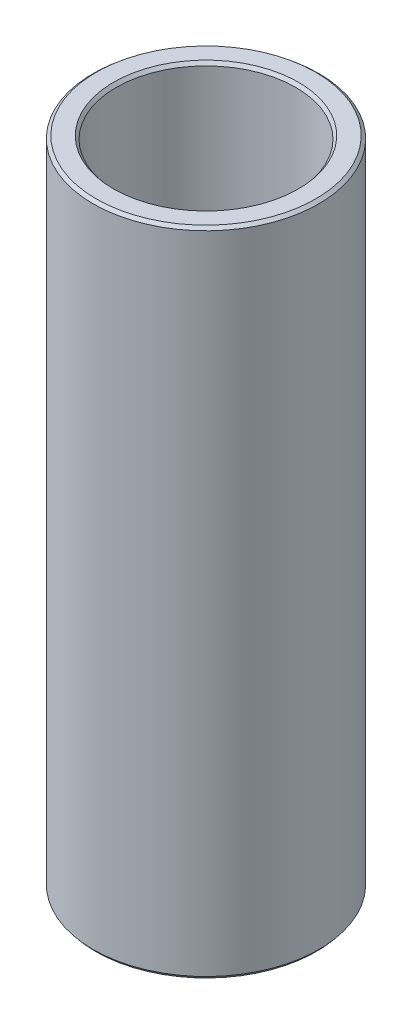
SolidWorks part; units mm, degrees
ref_plane "Front Plane" through (0, 0, 0) normal (0, 0, 1) x (1, 0, 0)
ref_plane "Top Plane" through (0, 0, 0) normal (0, 1, 0) x (1, 0, 0)
ref_plane "Right Plane" through (0, 0, 0) normal (1, 0, 0) x (0, 0, -1)
sketch "Sketch1" plane through (0, 0, 0) normal (0, 1, 0) x (1, 0, 0)
  circle A0 centre (0, 0) radius 57.5
  dimension "SLEEVE_OD" = 115
extrude "Boss-Extrude1" add sketch "Sketch1" along normal blind 331.8476
sketch "Sketch2" plane through (0, 0, 0) normal (0, 1, 0) x (1, 0, 0)
  circle A0 centre (0, 0) radius 45.7373
  dimension "BORE_D" = 91.4746
extrude "Cut-Extrude1" cut sketch "Sketch2" along normal through all
chamfer "Chamfer1" distance 1.3495 angle 50.075 4 edges at (0, 331.8476, 45.7373) (0, 0, 45.7373) (0, 0, 57.5) (0, 331.8476, 57.5) first distance on face at (0, 331.8476, 45.7373) first distance on face at (0, 0, 45.7373) first distance on face at (0, 331.8476, 57.5)
